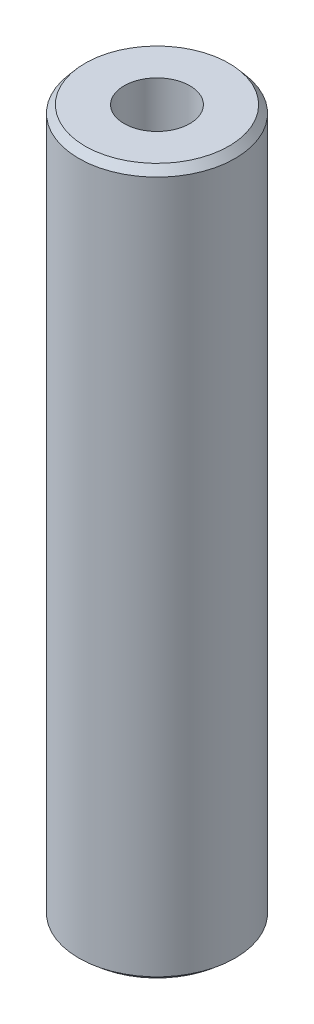
SolidWorks part; units mm, degrees
ref_plane "Front Plane" through (0, 0, 0) normal (0, 0, 1) x (1, 0, 0)
ref_plane "Top Plane" through (0, 0, 0) normal (0, 1, 0) x (1, 0, 0)
ref_plane "Right Plane" through (0, 0, 0) normal (1, 0, 0) x (0, 0, -1)
sketch "Sketch1" plane through (0, 0, 0) normal (0, 1, 0) x (1, 0, 0)
  circle A0 centre (0, 0) radius 7.5
  dimension "SHAFT_OD" = 15
extrude "Boss-Extrude1" add sketch "Sketch1" along normal blind 67.7421
sketch "Sketch2" plane through (0, 0, 0) normal (0, 1, 0) x (1, 0, 0)
  circle A0 centre (0, 0) radius 3.1509
  dimension "BORE_D" = 6.3019
extrude "Cut-Extrude1" cut sketch "Sketch2" along normal through all
chamfer "Chamfer1" distance 0.7172 angle 40.209 2 edges at (0, 67.7421, 7.5) (0, 0, 7.5) first distance on face at (0, 67.7421, 7.5) first distance on face at (0, 0, 3.1509)
